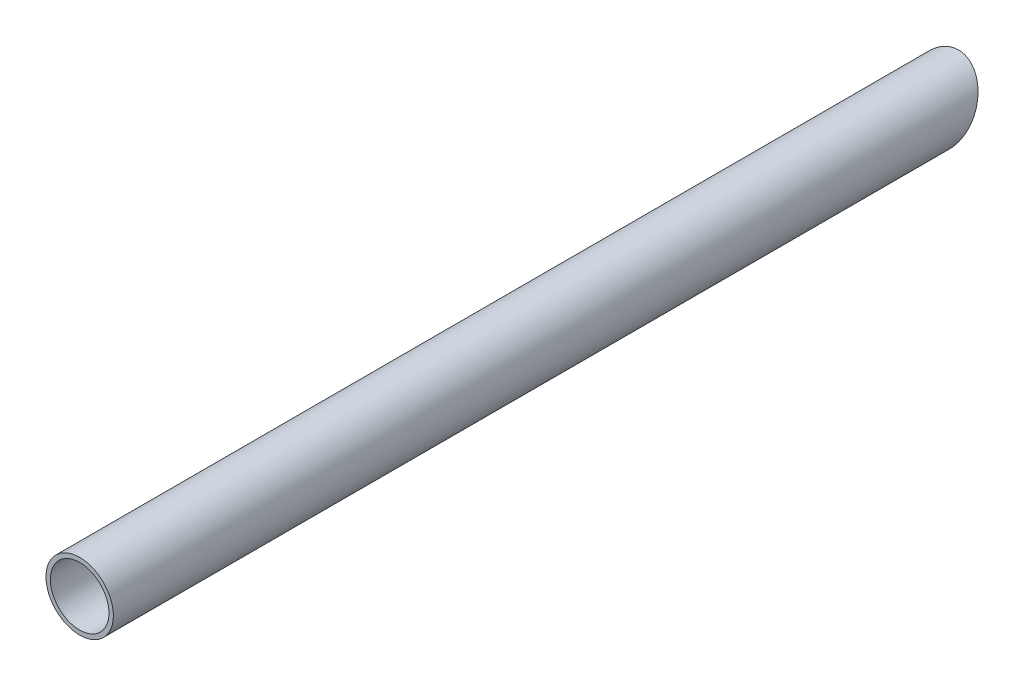
SolidWorks part; units mm, degrees
ref_plane "Front Plane" through (0, 0, 0) normal (0, 0, 1) x (1, 0, 0)
ref_plane "Top Plane" through (0, 0, 0) normal (0, 1, 0) x (1, 0, 0)
ref_plane "Right Plane" through (0, 0, 0) normal (1, 0, 0) x (0, 0, -1)
sketch "Sketch1" plane through (0, 0, 0) normal (0, 0, 1) x (1, 0, 0)
  circle A0 centre (0, 0) radius 10
  circle A1 centre (0, 0) radius 11.5
  dimension "D1" = 20
  dimension "D2" = 23
extrude "Boss-Extrude1" add sketch "Sketch1" along normal mid plane 300
sketch "Sketch2" plane through (0, 0, 0) normal (1, 0, 0) x (0, 0, -1)
  line L0 (150, 11.5) -> (136.7209, -11.5)
  line L1 (-150, -11.5) -> (150, -11.5) construction
  line L2 (136.7209, -11.5) -> (150, -11.5)
  line L3 (150, -11.5) -> (150, 11.5)
  dimension "D1" = 60
extrude "Cut-Extrude1" cut sketch "Sketch2" against normal mid plane 300
ref_axis "Axis1" through (0, 0, 1.7464) along (0, 0, -1)
